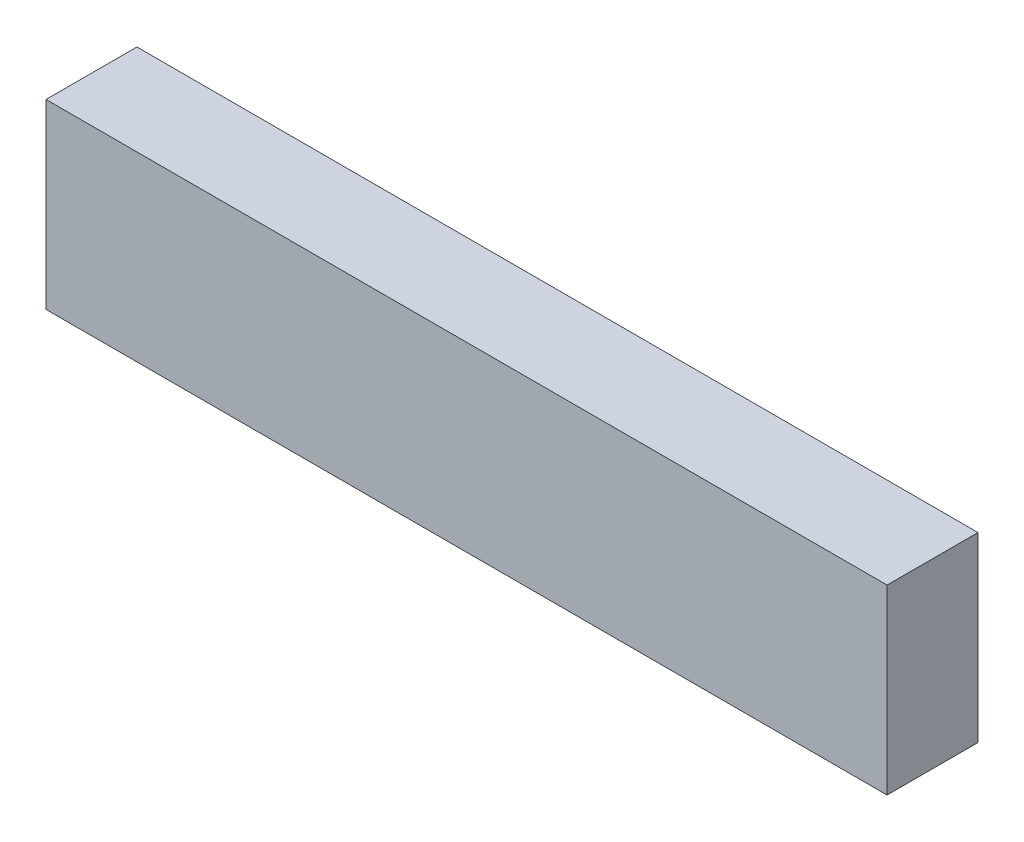
SolidWorks part; units mm, degrees
material "ABS"
ref_plane "Alzado" through (0, 0, 0) normal (0, 0, 1) x (1, 0, 0)
ref_plane "Planta" through (0, 0, 0) normal (0, 1, 0) x (1, 0, 0)
ref_plane "Vista lateral" through (0, 0, 0) normal (1, 0, 0) x (0, 0, -1)
sketch "Sketch1" plane through (0, 0, 0) normal (0, 0, 1) x (1, 0, 0)
  line L1 (-92.5, -20) -> (92.5, -20)
  line L2 (-92.5, -20) -> (-92.5, 20)
  line L3 (-92.5, 20) -> (92.5, 20)
  line L4 (92.5, -20) -> (92.5, 20)
  line L5 (-92.5, -20) -> (92.5, 20) construction
  line L6 (-92.5, 20) -> (92.5, -20) construction
  point P0 (0, 0)
  dimension "D1" = 185
  dimension "D2" = 40
extrude "Boss-Extrude1" add sketch "Sketch1" along normal blind 20
